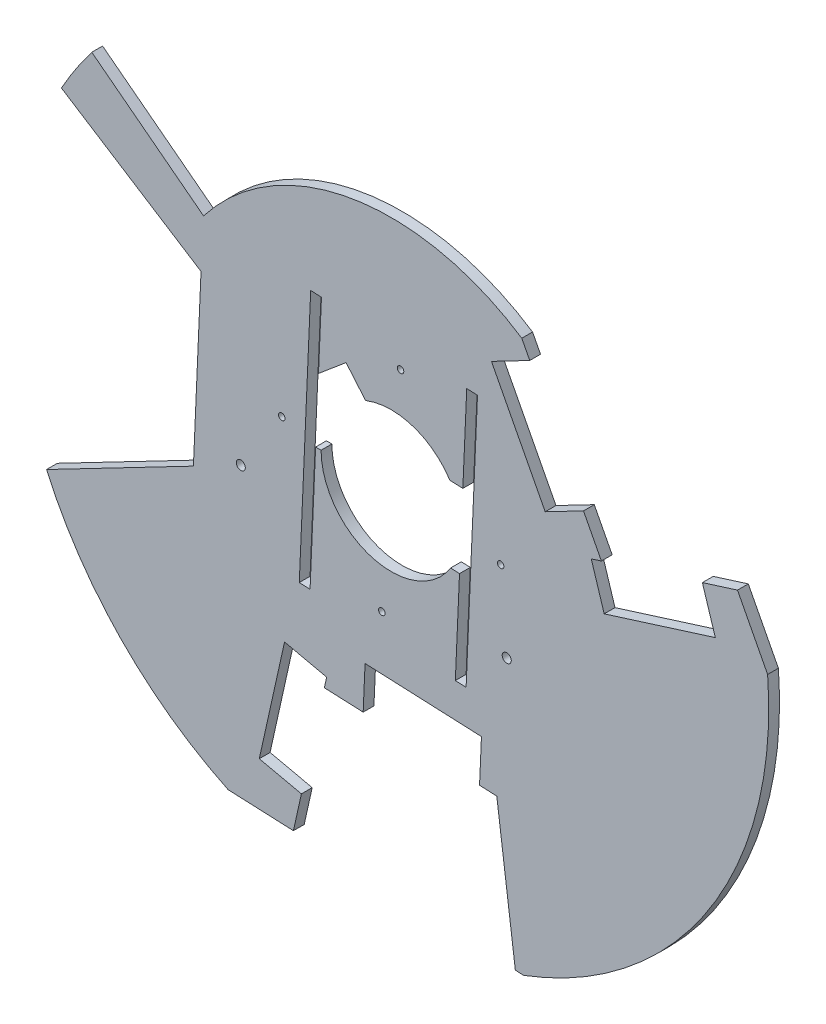
SolidWorks part; units mm, degrees
material "Balsa"
ref_plane "Plan de face" through (0, 0, 0) normal (0, 0, 1) x (1, 0, 0)
ref_plane "Plan de dessus" through (0, 0, 0) normal (0, 1, 0) x (1, 0, 0)
ref_plane "Plan de droite" through (0, 0, 0) normal (1, 0, 0) x (0, 0, -1)
sketch "Esquisse1" plane through (0, 0, 0) normal (0, 0, 1) x (1, 0, 0)
  line L0 (-11.9, 30.243) -> (-20.9197, 40.9503)
  line L1 (0, 0) -> (31.6699, 0) construction
  line L2 (-20.9197, 40.9503) -> (-33.7021, 30.1824)
  line L3 (174.4814, 13.462) -> (160.5092, 40.3333)
  line L4 (0, 0) -> (0, 32.5) construction
  line L5 (35.6001, -41.61) -> (34.7183, -61.5906) construction
  line L6 (-41.7246, -38.1976) -> (-36.7295, -38.418) construction
  line L7 (-41.7246, -38.1976) -> (-41.2837, -28.2073) construction
  line L8 (-41.2837, -28.2073) -> (-36.2886, -28.4277) construction
  line L9 (-36.7295, -38.418) -> (-36.2886, -28.4277) construction
  line L10 (34.7183, -61.5906) -> (40.0089, 58.2928)
  line L11 (-38.9773, 25.7386) -> (-11.9, 30.243) construction
  line L12 (-29.9576, 15.0314) -> (-20.9197, 40.9503) construction
  line L13 (0, 0) -> (-25.4386, 27.9908) construction
  line L14 (34.7183, -61.5906) -> (29.7232, -61.3701)
  line L15 (40.0089, 58.2928) -> (35.0138, 58.5132)
  line L16 (30.605, -41.3896) -> (35.6001, -41.61) construction
  line L17 (30.605, -41.3896) -> (31.0459, -31.3993) construction
  line L18 (35.6001, -41.61) -> (36.041, -31.6197) construction
  line L19 (31.0459, -31.3993) -> (36.041, -31.6197) construction
  line L20 (29.7232, -61.3701) -> (31.6607, -17.466)
  line L21 (-37.6113, -58.3986) -> (-42.6064, -58.1781)
  line L22 (-37.6113, -58.3986) -> (-35.0341, 0)
  line L23 (-42.6064, -58.1781) -> (-37.3158, 61.7052)
  line L24 (39.1272, 38.3122) -> (34.132, 38.5327) construction
  line L25 (39.1272, 38.3122) -> (38.6863, 28.3219) construction
  line L26 (34.132, 38.5327) -> (33.6911, 28.5424) construction
  line L27 (38.6863, 28.3219) -> (33.6911, 28.5424) construction
  line L28 (-32.3207, 61.4847) -> (-37.3158, 61.7052)
  line L29 (-38.9068, 25.6548) -> (-38.9773, 25.7386) construction
  line L30 (-38.9002, 25.8036) -> (-38.9773, 25.7386) construction
  line L31 (-33.7021, 30.1824) -> (-32.3207, 61.4847)
  line L32 (-33.2024, 41.5042) -> (-38.1976, 41.7246) construction
  line L33 (-33.2024, 41.5042) -> (-33.6433, 31.5139) construction
  line L34 (-38.1976, 41.7246) -> (-38.6385, 31.7344) construction
  line L35 (-33.6433, 31.5139) -> (-38.6385, 31.7344) construction
  line L36 (33.2038, 17.5) -> (35.0138, 58.5132)
  line L37 (-32.5, 0) -> (-35.0341, 0)
  line L38 (27.2154, 17.7643) -> (33.2038, 17.5)
  line L39 (27.5233, -17.2834) -> (31.6607, -17.466)
  line L40 (-38.1976, 41.7246) -> (39.1272, 38.3122) construction
  line L41 (-38.1976, 41.7246) -> (-41.7246, -38.1976) construction
  line L42 (39.1272, 38.3122) -> (35.6001, -41.61) construction
  line L43 (-41.7246, -38.1976) -> (35.6001, -41.61) construction
  line L44 (160.5092, 40.3333) -> (97.4284, 20.4765)
  line L45 (97.4284, 20.4765) -> (60.5218, 91.4547)
  line L46 (60.5218, 91.4547) -> (113.0069, 131.6888)
  line L47 (113.0069, 131.6888) -> (111.2327, 135.101)
  line L49 (61.3846, -163.8808) -> (57.5424, -163.7113)
  line L50 (57.5424, -163.7113) -> (48.9412, -98.1408)
  line L51 (48.9412, -98.1408) -> (-30.981, -94.6137)
  line L52 (-30.981, -94.6137) -> (-45.325, -159.1716)
  line L53 (-45.325, -159.1716) -> (-75.5823, -157.8364)
  arc A0 (111.2327, 135.101) -> (-75.5823, -157.8364) centre (0, 0) ccw
  arc A1 (-32.5, 0) -> (27.5233, -17.2834) centre (0, 0) ccw
  arc A2 (27.2154, 17.7643) -> (-11.9, 30.243) centre (0, 0) ccw
  arc A3 (61.3846, -163.8808) -> (174.4814, 13.462) centre (0, 0) ccw
  circle A4 centre (121.4843, 17.5652) radius 4.7
  circle A5 centre (67.7962, 55.7884) radius 4.7
  circle A6 centre (14.4161, -86.6074) radius 4.7
  circle A7 centre (-45.5303, -113.9911) radius 4.7
  dimension "D1" = 65
  dimension "D2" = 87.845
  dimension "D3" = 42.265
  dimension "D4" = 14
  dimension "D5" = 10
  dimension "D6" = 57.18
  dimension "D7" = 5
  dimension "D8" = 20
  dimension "D9" = 20
  dimension "D11" = 35
  dimension "D12" = 17.5
extrude "Boss.-Extru.1" add sketch "Esquisse1" along normal blind 5 contours A0 A2 L36 L15 L10 L14 L20 A1 L22 L21 L23 L29 L30 L28 L31 L2 L0 region at (143.4418, -91.4771, 0)
sketch "Esquisse2" plane through (0, 0, 5) normal (0, 0, 1) x (1, 0, 0)
  line L0 (-88.149, 43.929) -> (-152.8606, 85.1976)
  line L1 (-88.149, 43.929) -> (-91.676, -35.9932)
  line L2 (-91.676, -35.9932) -> (-159.7715, -71.4008)
  line L3 (0, 0) -> (0, 85.1976) construction
  line L5 (0, 0) -> (-89.9125, 3.9679) construction
  circle A0 centre (0, 0) radius 175 construction
  arc A1 (-152.8606, 85.1976) -> (-159.7715, -71.4008) centre (0, 0) ccw
  dimension "D1" = 90
  dimension "D2" = 80
  dimension "D3" = 120
  dimension "D4" = 87.473
extrude "Enlèv. mat.-Extru.1" cut sketch "Esquisse2" against normal blind 10
sketch "Esquisse3" plane through (0, 0, 5) normal (0, 0, 1) x (1, 0, 0)
  line L0 (14.4161, -86.6074) -> (41.3898, -87.7978) construction
  line L1 (48.9412, -98.1408) -> (-30.981, -94.6137) construction
  line L2 (40.949, -97.7881) -> (-12.9985, -95.4073)
  line L3 (40.949, -97.7881) -> (41.8307, -77.8075)
  line L4 (-12.9985, -95.4073) -> (-12.1168, -75.4267)
  line L5 (41.8307, -77.8075) -> (-12.1168, -75.4267)
  line L6 (-45.5303, -113.9911) -> (-39.6741, -87.6339) construction
  line L7 (-30.981, -94.6137) -> (-45.325, -159.1716) construction
  line L8 (-49.436, -85.4649) -> (-29.9121, -89.8028)
  line L9 (-49.436, -85.4649) -> (-61.1485, -138.1794)
  line L10 (-29.9121, -89.8028) -> (-41.6246, -142.5173)
  line L11 (-61.1485, -138.1794) -> (-41.6246, -142.5173)
  line L12 (64.2125, 84.3569) -> (89.1244, 36.4466)
  line L13 (64.2125, 84.3569) -> (46.4679, 75.1302)
  line L14 (89.1244, 36.4466) -> (71.3799, 27.2199)
  line L15 (46.4679, 75.1302) -> (71.3799, 27.2199)
  line L16 (98.7328, -0.0804) -> (92.7276, 18.9968)
  line L17 (98.7328, -0.0804) -> (150.2411, 16.1336)
  line L18 (92.7276, 18.9968) -> (144.2359, 35.2107)
  line L19 (150.2411, 16.1336) -> (144.2359, 35.2107)
  line L20 (67.7962, 55.7884) -> (55.3402, 79.7435) construction
  line L21 (121.4843, 17.5652) -> (95.7302, 9.4582) construction
  line L22 (160.5092, 40.3333) -> (97.4284, 20.4765) construction
  line L23 (97.4284, 20.4765) -> (60.5218, 91.4547) construction
  point P33 (0, 0)
  dimension "D1" = 20
  dimension "D2" = 54
  dimension "D3" = 27
  dimension "D4" = 20
  dimension "D5" = 54
  dimension "D6" = 27
  dimension "D7" = 2
extrude "Enlèv. mat.-Extru.2" cut sketch "Esquisse3" against normal blind 10
sketch "Esquisse4" plane through (0, 0, 5) normal (0, 0, 1) x (1, 0, 0)
  line L0 (-138.7868, 106.5984) -> (-86.9733, 66.8018)
  line L1 (-88.149, 43.929) -> (-152.8606, 85.1976) construction
  line L2 (60.5218, 91.4547) -> (113.0069, 131.6888) construction
  line L3 (60.5218, 91.4547) -> (113.0069, 131.6888)
  line L4 (113.0069, 131.6888) -> (111.2327, 135.101)
  line L5 (113.0069, 131.6888) -> (111.2327, 135.101) construction
  arc A0 (111.2327, 135.101) -> (-152.8606, 85.1976) centre (0, 0) ccw construction
  arc A1 (-86.9733, 66.8018) -> (60.5218, 91.4547) centre (0, 0) cw
  arc A2 (-138.7868, 106.5984) -> (111.2327, 135.101) centre (0, 0) cw
  dimension "D1" = 5
extrude "Enlèv. mat.-Extru.3" cut sketch "Esquisse4" against normal blind 10
hole_wizard "Trou taraudé M51" positions "Esquisse5" profile "Esquisse6" tap size "M5" standard "ISO" end condition through all
sketch "Esquisse5" plane through (0, 0, 5) normal (0, 0, 1) x (0.999, -0.0441, 0)
  point P0 (-68.569, -27.6625)
  point P2 (55.2809, -37.9834)
  point P4 (-87.2993, 135.5593)
sketch "Esquisse6" plane through (-69.7219, -24.6126, 5) normal (1, 0, 0) x (0, -1, 0)
  line L0 (0, 0) -> (0, 5)
  line L1 (0, 5) -> (2.1, 5)
  line L2 (2.1, 5) -> (2.1, 0)
  line L3 (2.1, 0) -> (0, 0)
  line L4 (0, -6.35) -> (0, 107.95) construction
  dimension "Diamètre principal du filetage" = 4.2
  dimension "Profondeur du trou pour taraudage jusqu'au prochain" = 5
sketch "Esquisse7" plane through (0, 0, 5) normal (0, 0, 1) x (1, 0, 0)
  line L0 (50.7264, -4.3394) -> (4.3394, 50.7264) construction
  line L1 (50.7264, -4.3394) -> (-4.3394, -50.7264) construction
  line L2 (4.3394, 50.7264) -> (-50.7264, 4.3394) construction
  line L3 (-4.3394, -50.7264) -> (-50.7264, 4.3394) construction
  line L4 (50.7264, -4.3394) -> (-50.7264, 4.3394) construction
  line L5 (4.3394, 50.7264) -> (-4.3394, -50.7264) construction
  line L6 (-20.9197, 40.9503) -> (-33.7021, 30.1824) construction
  circle A0 centre (-50.7264, 4.3394) radius 1.5
  circle A1 centre (4.3394, 50.7264) radius 1.5
  circle A2 centre (50.7264, -4.3394) radius 1.5
  circle A3 centre (-4.3394, -50.7264) radius 1.5
  point P1 (0, 0)
  dimension "D2" = 3
  dimension "D1" = 72
extrude "Enlèv. mat.-Extru.4" cut sketch "Esquisse7" against normal blind 10
